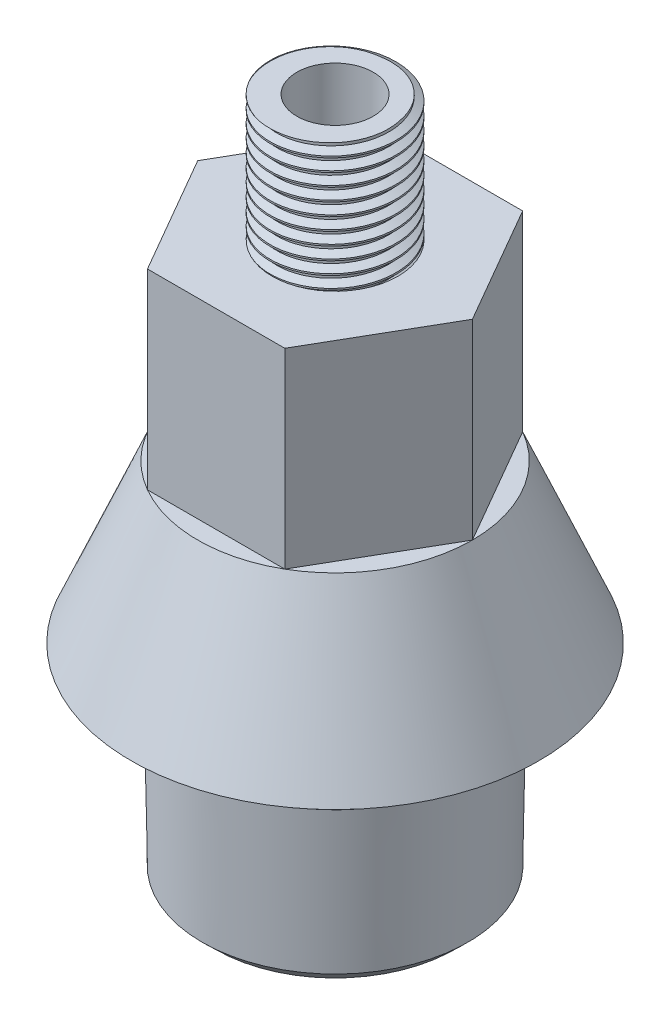
SolidWorks part; units mm, degrees
material "Plain Carbon Steel"
ref_plane "Front Plane" through (0, 0, 0) normal (0, 0, 1) x (1, 0, 0)
ref_plane "Top Plane" through (0, 0, 0) normal (0, 1, 0) x (1, 0, 0)
ref_plane "Right Plane" through (0, 0, 0) normal (1, 0, 0) x (0, 0, -1)
sketch "Sketch1" plane through (0, 0, 0) normal (0, 1, 0) x (1, 0, 0)
  line L1 (13.6968, 0) -> (6.8484, 11.8618)
  line L2 (6.8484, 11.8618) -> (-6.8484, 11.8618)
  line L3 (-6.8484, 11.8618) -> (-13.6968, 0)
  line L4 (-13.6968, 0) -> (-6.8484, -11.8618)
  line L5 (-6.8484, -11.8618) -> (6.8484, -11.8618)
  line L6 (6.8484, -11.8618) -> (13.6968, 0)
  circle A0 centre (0, 0) radius 11.8618 construction
  dimension "D1" = 23.7236
extrude "Boss-Extrude1" add sketch "Sketch1" along normal blind 19.0754
sketch "Sketch2" plane through (0, 19.0754, 0) normal (0, 1, 0) x (1, 0, 0)
  circle A0 centre (0, 0) radius 6.2738
  dimension "D1" = 12.5476
extrude "Boss-Extrude2" add sketch "Sketch2" along normal blind 12.5857
ref_plane "Plane1" through (0, -15.748, 0) normal (0, -1, 0) x (-1, 0, 0)
sketch "Sketch3" plane through (0, 0, 0) normal (0, -1, 0) x (1, 0, 0)
  circle A0 centre (0, 0) radius 13.6968
sketch "Sketch4" plane through (0, -15.748, 0) normal (0, -1, 0) x (-1, 0, 0)
  circle A0 centre (0, 0) radius 20.3327
  dimension "D1" = 40.6654
loft "Loft1" add profiles "Sketch3", "Sketch4"
sketch "Sketch5" plane through (0, -15.748, 0) normal (0, -1, 0) x (1, 0, 0)
  circle A1 centre (0, 0) radius 20.3327
  circle A2 centre (0, 0) radius 20.3327
  dimension "D1" = 0
ref_plane "Plane3" through (0, -20.5994, 0) normal (0, -1, 0) x (-1, 0, 0)
sketch "Sketch6" plane through (0, -20.5994, 0) normal (0, -1, 0) x (-1, 0, 0)
  circle A0 centre (0, 0) radius 13.5001
  dimension "D1" = 27.0002
loft "Loft2" add profiles "Sketch6" section "Sketch6" section face at (0, -15.748, -20.3327)
sketch "Sketch8" plane through (0, -20.5994, 0) normal (0, -1, 0) x (1, 0, 0)
  circle A0 centre (0, 0) radius 13.5001
extrude "Boss-Extrude3" add sketch "Sketch8" along normal blind 15.6337 draft 1
chamfer "Chamfer1" distance 1.27 angle 45 1 edges at (0, -36.2331, -13.2272)
thread "Thread1" pitch 1.27 start angle 0, offset 3.54, length 0, pitch 1.27, diameter 12.5476
ref_plane "Plane4" through (-6.2738, 35.2011, 0) normal (0, 0, 1) x (-1, 0, 0)
sketch "Thread Profile1" plane through (-6.2738, 35.2011, 0) normal (0, 0, 1) x (-1, 0, 0)
  line L0 (0, 0) -> (0, 1.27) construction
  line L11 (0, 0) -> (0, 1.1112)
  line L12 (0, 1.1112) -> (-0.6874, 0.7144)
  line L13 (-0.6874, 0.7144) -> (-0.6874, 0.3969)
  line L15 (-0.6874, 0.3969) -> (0, 0)
  line L17 (-0.6874, 0.5556) -> (0, 0.5556) construction
  point P2 (0, 0)
  dimension "Pitch" = 1.27
  dimension "Profile_Angle" = 60
  dimension "Profile_Land" = 0.3175
  dimension "Profile_Height" = 0.6874
sketch "Sketch12" plane through (0, 0, 0) normal (0, 0, 1) x (1, 0, 0)
  line L0 (17.309, -17.8949) -> (4.6029, 0)
  line L3 (0, 0) -> (0, -20.5994) construction
  line L4 (-13.5001, -20.5994) -> (13.5001, -20.5994) construction
  line L5 (13.5001, -20.5994) -> (20.3327, -15.748) construction
  line L8 (-6.8485, 0) -> (6.8483, 0) construction
  line L9 (17.309, -17.8949) -> (20.2084, -15.8362)
  line L10 (20.2084, -15.8362) -> (7.5024, 2.0587)
  line L11 (7.5024, 2.0587) -> (4.6029, 0)
  dimension "D1" = 3.7084
  dimension "D2" = 3.556
revolve "Cut-Revolve1" cut sketch "Sketch12" angle 360 about L0
pattern_circular "CirPattern1" count 2 over 360 about axis through (0, -15.748, 0) along (0, -1, 0) of "Cut-Revolve1"
sketch "Sketch13" plane through (0, 31.6611, 0) normal (0, 1, 0) x (1, 0, 0)
  circle A0 centre (0, 0) radius 3.81
  dimension "D1" = 7.62
extrude "Cut-Extrude1" cut sketch "Sketch13" against normal blind 47.3837
hole_wizard "Tap Drill for 5/8-11 Tap1" positions "Sketch14" profile "Sketch16" hole size "5/8-11" standard "ANSI Inch"
sketch "Sketch14" plane through (0, -36.2331, 0) normal (0, -1, 0) x (-1, 0, 0)
  point P0 (0, 0)
sketch "Sketch16" plane through (0, -36.2331, 0) normal (1, 0, 0) x (0, 0, -1)
  line L0 (0, 0) -> (0, 24.3205)
  line L1 (0, 24.3205) -> (6.7462, 20.267)
  line L2 (6.7462, 20.267) -> (6.7462, 0)
  line L5 (6.7462, 0) -> (0, 0)
  line L10 (0, 24.3205) -> (-6.7462, 20.267) construction
  line L11 (0, -6.35) -> (0, 107.95) construction
  dimension "Hole Dia." = 13.4925
  dimension "Hole Depth" = 24.3205
  dimension "Drill Angle" = 118
